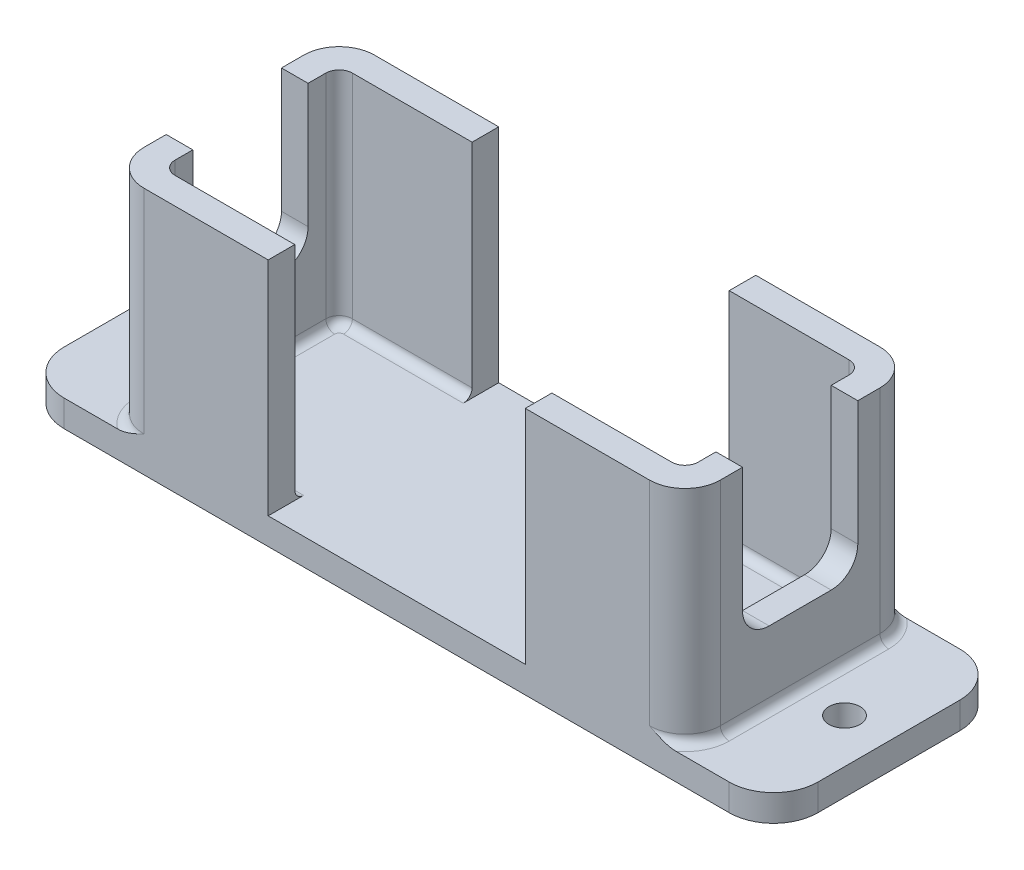
SolidWorks part; units mm, degrees
material "Acrílico (Impacto medio-alto)"
ref_plane "Alzado" through (0, 0, 0) normal (0, 0, 1) x (1, 0, 0)
ref_plane "Planta" through (0, 0, 0) normal (0, 1, 0) x (1, 0, 0)
ref_plane "Vista lateral" through (0, 0, 0) normal (1, 0, 0) x (0, 0, -1)
sketch "Croquis1" plane through (0, 0, 0) normal (0, 1, 0) x (1, 0, 0)
  line L0 (0, -13) -> (0, 13)
  line L1 (0, 13) -> (18, 13)
  line L2 (18, 13) -> (18, 10)
  line L3 (18, 10) -> (3, 10)
  line L4 (3, 10) -> (3, -10)
  line L5 (3, -10) -> (18, -10)
  line L6 (18, -10) -> (18, -13)
  line L7 (18, -13) -> (0, -13)
  line L8 (32.5, 13) -> (32.5, -12.2003) construction
  line L9 (47, -10) -> (47, -13)
  line L10 (62, -10) -> (47, -10)
  line L11 (62, 10) -> (62, -10)
  line L12 (47, 10) -> (62, 10)
  line L13 (47, 13) -> (47, 10)
  line L14 (65, 13) -> (47, 13)
  line L15 (65, -13) -> (65, 13)
  line L16 (47, -13) -> (65, -13)
  point P3 (0, 0)
  dimension "D1" = 3
  dimension "D2" = 3
  dimension "D3" = 3
  dimension "D4" = 20
  dimension "D5" = 15
  dimension "D6" = 14.5
extrude "Saliente-Extruir1" add sketch "Croquis1" along normal blind 25
sketch "Croquis2" plane through (0, 0, 0) normal (0, -1, 0) x (1, 0, 0)
  line L12 (-10, -13) -> (75, -13)
  line L13 (-10, -13) -> (-10, 13)
  line L14 (-10, 13) -> (75, 13)
  line L15 (75, -13) -> (75, 13)
  line L16 (47, 13) -> (65, 13) construction
  line L17 (18, -13) -> (0, -13) construction
  line L18 (0, -13) -> (0, 13) construction
  line L19 (65, 13) -> (65, -13) construction
  dimension "D1" = 10
  dimension "D2" = 10
extrude "Saliente-Extruir2" add sketch "Croquis2" along normal blind 3
sketch "Croquis3" plane through (0, 0, 0) normal (-1, 0, 0) x (0, 0, 1)
  line L0 (-13, 25) -> (13, 25) construction
  line L1 (-6.5, 25) -> (6.5, 25)
  line L2 (-6.5, 25) -> (-6.5, 8)
  line L3 (-6.5, 8) -> (6.5, 8)
  line L4 (6.5, 25) -> (6.5, 8)
  line L6 (-13, 0) -> (13, 0) construction
  point P6 (0, 25)
  dimension "D1" = 13
  dimension "D2" = 8
ref_plane "Plano2" through (32.5, 0, 0) normal (1, 0, 0) x (0, 0, -1)
extrude "Cortar-Extruir2" cut sketch "Croquis3" against normal through all
fillet "Redondeo1" radius 5 4 edges at (-10, -1.5, 13) (-10, -1.5, -13) (75, -1.5, -13) (75, -1.5, 13)
fillet "Redondeo2" radius 3 2 edges at (1.5, 8, -6.5) (1.5, 8, 6.5)
fillet "Redondeo3" radius 3 2 edges at (63.5, 8, 6.5) (63.5, 8, -6.5)
fillet "Redondeo4" radius 1.5 2 edges at (3, 12.5, -10) (3, 12.5, 10)
fillet "Redondeo5" radius 4 2 edges at (0, 12.5, 13) (0, 12.5, -13)
fillet "Redondeo6" radius 4 2 edges at (65, 12.5, -13) (65, 12.5, 13)
fillet "Redondeo7" radius 1.5 2 edges at (62, 12.5, 10) (62, 12.5, -10)
sketch "Croquis5" plane through (0, 0, 0) normal (0, 1, 0) x (1, 0, 0)
  line L2 (75, 8) -> (75, -8) construction
  line L3 (-10, -8) -> (-10, 8) construction
  circle A0 centre (70, 0) radius 1.75
  circle A1 centre (-5, 0) radius 1.75
  dimension "D1" = 3.5
  dimension "D2" = 5
  dimension "D3" = 5
extrude "Cortar-Extruir3" cut sketch "Croquis5" against normal through all
combine bodies "Combinar1" operation type add bodies to combine 112 111
fillet "Redondeo8" radius 1 6 edges at (1.1716, 0, -11.8284) (1.1716, 0, 11.8284) (0, 0, 0) (63.8284, 0, 11.8284) (63.8284, 0, -11.8284) (65, 0, 0)
fillet "Redondeo10" radius 1 10 edges at (53.75, 0, -10) (61.5607, 0, -9.5607) (53.75, 0, 10) (61.5607, 0, 9.5607) (11.25, 0, 10) (3.4393, 0, 9.5607) (11.25, 0, -10) (3.4393, 0, -9.5607) (62, 0, 0) (3, 0, 0)
ref_plane "Plano3" through (32.5, 0, 0) normal (1, 0, 0) x (0, 0, -1)
